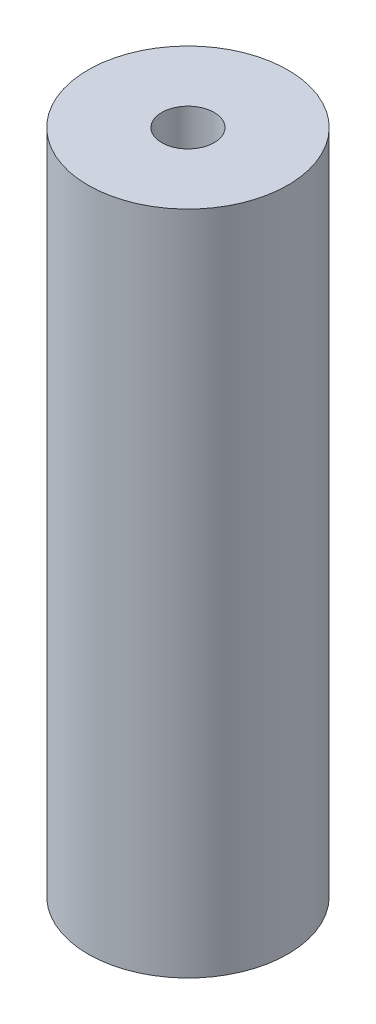
SolidWorks part; units mm, degrees
material "6061-T6 (SS)"
ref_plane "Front Plane" through (0, 0, 0) normal (0, 0, 1) x (1, 0, 0)
ref_plane "Top Plane" through (0, 0, 0) normal (0, 1, 0) x (1, 0, 0)
ref_plane "Right Plane" through (0, 0, 0) normal (1, 0, 0) x (0, 0, -1)
sketch "Sketch1" plane through (0, 0, 0) normal (0, 1, 0) x (1, 0, 0)
  circle A0 centre (0, 0) radius 6
  dimension "D1" = 12
extrude "Boss-Extrude1" add sketch "Sketch1" along normal blind 40
sketch "Sketch4" plane through (0, 40, 0) normal (0, 1, 0) x (1, 0, 0)
  point P0 (0, 0)
hole_wizard "Tap Drill for M3 Helicoil1" positions "Sketch4" profile "Sketch3" hole size "M3x0.5" standard "DIN" end condition through all
sketch "Sketch3" plane through (0, 40, 0) normal (1, 0, 0) x (0, 0, 1)
  line L0 (0, 0) -> (0, 40)
  line L1 (0, 40) -> (1.575, 40)
  line L2 (1.575, 40) -> (1.575, 0)
  line L5 (1.575, 0) -> (0, 0)
  line L11 (0, -6.35) -> (0, 107.95) construction
  dimension "Thru Hole Dia." = 3.15
  dimension "Thru Hole Depth" = 40
